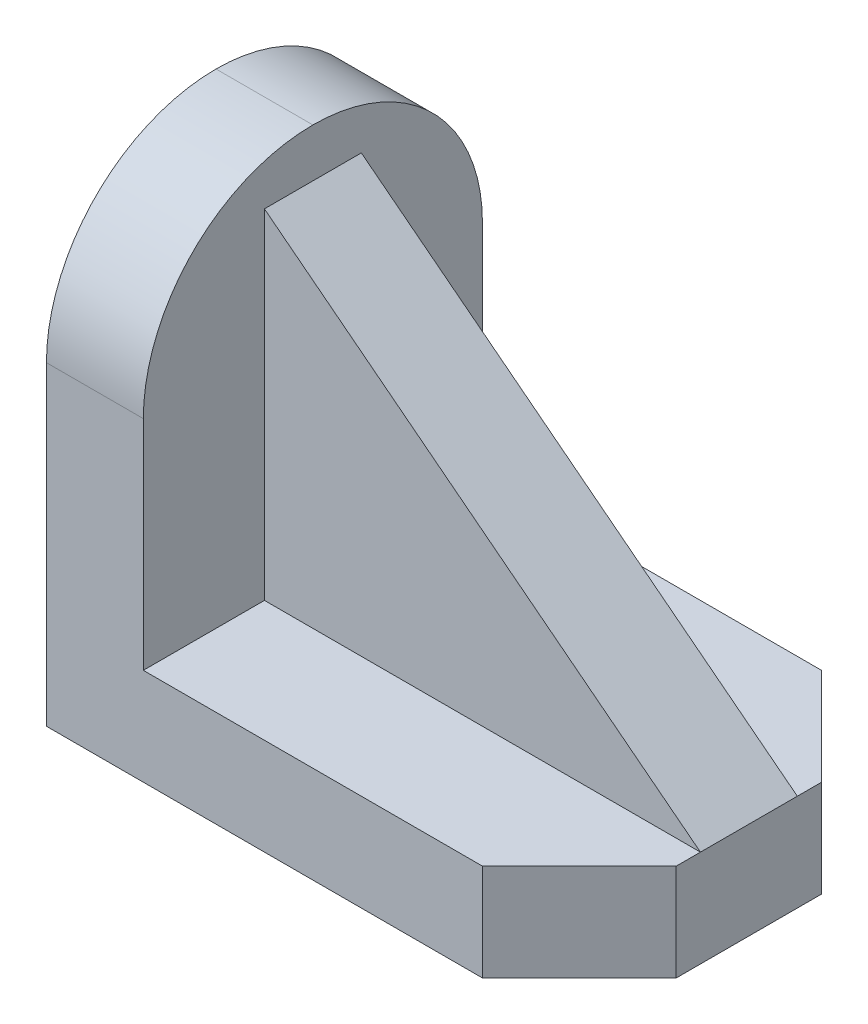
SolidWorks part; units mm, degrees
material "Alloy Steel"
ref_plane "Front Plane" through (0, 0, 0) normal (0, 0, 1) x (1, 0, 0)
ref_plane "Top Plane" through (0, 0, 0) normal (0, 1, 0) x (1, 0, 0)
ref_plane "Right Plane" through (0, 0, 0) normal (1, 0, 0) x (0, 0, -1)
sketch "Sketch1" plane through (0, 0, 0) normal (0, 1, 0) x (1, 0, 0)
  line L1 (0, 0) -> (1676.4, 0)
  line L2 (0, 0) -> (0, 1066.8)
  line L3 (0, 1066.8) -> (1676.4, 1066.8)
  line L4 (1676.4, 0) -> (1676.4, 1066.8)
  dimension "D1" = 1676.4
  dimension "D2" = 1066.8
extrude "Boss-Extrude1" add sketch "Sketch1" along normal blind 304.8
sketch "Sketch2" plane through (0, 0, 0) normal (-1, 0, 0) x (0, 0, 1)
  line L1 (-1066.8, 0) -> (0, 0)
  line L2 (-1066.8, 0) -> (-1066.8, 1524)
  line L3 (-1066.8, 1524) -> (0, 1524)
  line L4 (0, 0) -> (0, 1524)
  point P5 (0, 0)
  dimension "D1" = 1524
extrude "Boss-Extrude2" add sketch "Sketch2" against normal blind 304.8
fillet "Fillet1" radius 533.4 2 edges at (152.4, 1524, -1066.8) (152.4, 1524, 0)
sketch "Sketch5" plane through (0, 304.8, 0) normal (0, 1, 0) x (1, 0, 0)
  line L0 (304.8, 1066.8) -> (304.8, 0) construction
  line L1 (304.8, 685.8) -> (1676.4, 685.8)
  line L2 (304.8, 685.8) -> (304.8, 381)
  line L3 (304.8, 381) -> (1676.4, 381)
  line L4 (1676.4, 685.8) -> (1676.4, 381)
  line L5 (304.8, 0) -> (1676.4, 0) construction
  dimension "D1" = 304.8
  dimension "D2" = 381
  dimension "D3" = 1371.6
extrude "Boss-Extrude3" add sketch "Sketch5" along normal blind 1066.8
sketch "Sketch6" plane through (0, 0, -381) normal (0, 0, 1) x (1, 0, 0)
  line L0 (304.8, 1371.6) -> (1676.4, 304.8)
  line L1 (1676.4, 304.8) -> (1676.4, 1371.6)
  line L2 (1676.4, 1371.6) -> (304.8, 1371.6)
extrude "Cut-Extrude1" cut sketch "Sketch6" against normal blind 1066.8
chamfer "Chamfer1" distance 304.8 2 edges at (1676.4, 152.4, -1066.8) (1676.4, 152.4, 0)
